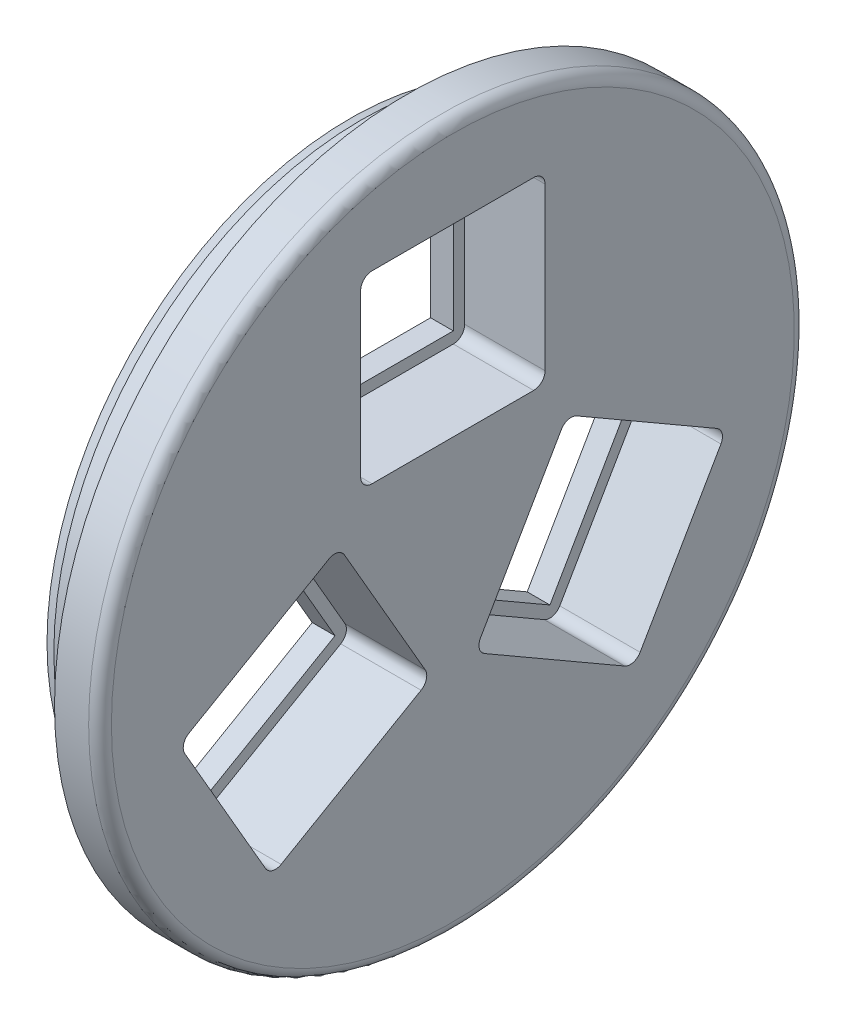
SolidWorks part; units mm, degrees
ref_plane "Front" through (0, 0, 0) normal (0, 0, 1) x (1, 0, 0)
ref_plane "Top" through (0, 0, 0) normal (0, 1, 0) x (1, 0, 0)
ref_plane "Right" through (0, 0, 0) normal (1, 0, 0) x (0, 0, -1)
sketch "Çizim1" plane through (0, 0, 0) normal (0, 0, 1) x (1, 0, 0)
  line L0 (0, 0) -> (45.3, 0) construction
  line L1 (48.1633, 0) -> (48.1633, 55.2041) construction
  line L2 (0, 0) -> (0, 55.2041) construction
  line L3 (0, 31) -> (5, 31)
  line L4 (0, 31) -> (0, 133)
  line L5 (5, 135) -> (25.3, 135)
  line L6 (25.3, 31) -> (25.3, 16)
  line L7 (25.3, 16) -> (35.3, 16)
  line L8 (45.3, 0) -> (45.3, 148.5)
  line L10 (40.3, 155) -> (25.3, 155)
  line L11 (25.3, 155) -> (25.3, 135)
  line L12 (7.3, 31) -> (25.3, 31)
  line L13 (5, 32.75) -> (7.3, 32.75)
  line L14 (5, 32.75) -> (5, 31)
  line L16 (7.3, 32.75) -> (7.3, 31)
  line L17 (0, 133) -> (5, 135)
  line L18 (35.3, 16) -> (35.3, 0)
  line L19 (35.3, 0) -> (45.3, 0)
  line L20 (45.3, 148.5) -> (45.3, 150)
  arc A0 (40.3, 155) -> (45.3, 150) centre (40.3, 150) cw
  point P8 (0, 135)
  point P24 (45.3, 155)
  dimension "D15" = 5
  dimension "D1" = 31
  dimension "D2" = 25.3
  dimension "D3" = 135
  dimension "D4" = 20
  dimension "D5" = 32
  dimension "D6" = 20
  dimension "D7" = 155
  dimension "D8" = 5
  dimension "D9" = 2.3
  dimension "D10" = 32.75
  dimension "D11" = 5
  dimension "D12" = 2
  dimension "D13" = 10
  dimension "D14" = 6.5
revolve "Döndür1" add sketch "Çizim1" angle 360 about L0
sketch "Sketch2" plane through (0, 0, 0) normal (-1, 0, 0) x (0, 0, 1)
  line L0 (0, 0) -> (0, 75)
  line L1 (-35.5, 110.5) -> (-35.5, 39.5)
  line L2 (-35.5, 115.5) -> (35.5, 115.5)
  line L3 (-40.5, 110.5) -> (-40.5, 39.5)
  line L4 (-35.5, 34.5) -> (35.5, 34.5)
  line L5 (40.5, 110.5) -> (40.5, 39.5)
  line L6 (-40.5, 115.5) -> (40.5, 34.5) construction
  line L7 (-40.5, 34.5) -> (40.5, 115.5) construction
  line L8 (-35.5, 39.5) -> (35.5, 39.5)
  line L9 (35.5, 110.5) -> (35.5, 39.5)
  line L10 (-35.5, 110.5) -> (35.5, 110.5)
  line L11 (115.9458, -20.176) -> (54.458, 15.324)
  line L12 (117.7759, -27.0061) -> (82.2759, -88.4939)
  line L13 (75.4458, -90.324) -> (13.958, -54.824)
  line L14 (47.6279, 13.4939) -> (12.1279, -47.9939)
  line L15 (-75.4458, -90.324) -> (-13.958, -54.824)
  line L16 (-82.2759, -88.4939) -> (-117.7759, -27.0061)
  line L17 (-115.9458, -20.176) -> (-54.458, 15.324)
  line L18 (-12.1279, -47.9939) -> (-47.6279, 13.4939)
  arc A0 (35.5, 115.5) -> (40.5, 110.5) centre (35.5, 110.5) cw
  arc A1 (35.5, 34.5) -> (40.5, 39.5) centre (35.5, 39.5) ccw
  arc A2 (-35.5, 34.5) -> (-40.5, 39.5) centre (-35.5, 39.5) cw
  arc A3 (-40.5, 110.5) -> (-35.5, 115.5) centre (-35.5, 110.5) cw
  arc A4 (-35.5, 39.5) -> (-35.5, 39.5) centre (-35.5, 39.5) cw
  arc A5 (35.5, 39.5) -> (35.5, 39.5) centre (35.5, 39.5) ccw
  arc A6 (35.5, 110.5) -> (35.5, 110.5) centre (35.5, 110.5) cw
  arc A7 (-35.5, 110.5) -> (-35.5, 110.5) centre (-35.5, 110.5) cw
  arc A8 (115.9458, -20.176) -> (117.7759, -27.0061) centre (113.4458, -24.5061) cw
  arc A9 (47.6279, 13.4939) -> (54.458, 15.324) centre (51.958, 10.9939) cw
  arc A10 (82.2759, -88.4939) -> (75.4458, -90.324) centre (77.9458, -85.9939) cw
  arc A11 (12.1279, -47.9939) -> (13.958, -54.824) centre (16.458, -50.4939) ccw
  arc A12 (-75.4458, -90.324) -> (-82.2759, -88.4939) centre (-77.9458, -85.9939) cw
  arc A13 (-12.1279, -47.9939) -> (-13.958, -54.824) centre (-16.458, -50.4939) cw
  arc A14 (-117.7759, -27.0061) -> (-115.9458, -20.176) centre (-113.4458, -24.5061) cw
  arc A15 (-47.6279, 13.4939) -> (-54.458, 15.324) centre (-51.958, 10.9939) ccw
  point P58 (0, 0)
  dimension "D3" = 5
  dimension "D1" = 81
  dimension "D2" = 81
  dimension "D4" = 5
extrude "Cut-Extrude2" cut sketch "Sketch2" against normal through all from offset 10 contours A3 L3 A2 L4 L8 L1 L10 L9 A1 L5 A0 L2 | L10 L1 L8 L9 | L14 A11 L13 A10 L12 A8 L11 A9 | L18 A15 L17 A14 L16 A12 L15 A13 region at (0, 40.5041, -17.75) region at (0, 35.6455, -17.75) region at (0, -37.5, 64.9519) region at (0, -37.5, -64.9519) offset against normal yes
sketch "Sketch4" plane through (0, 0, 0) normal (-1, 0, 0) x (0, 0, 1)
  line L0 (0, 0) -> (0, 75)
  line L1 (113.4458, -24.5061) -> (51.958, 10.9939)
  line L2 (-35.5, 110.5) -> (35.5, 110.5)
  line L3 (-35.5, 110.5) -> (-35.5, 39.5)
  line L4 (-35.5, 39.5) -> (35.5, 39.5)
  line L5 (35.5, 110.5) -> (35.5, 39.5)
  line L6 (-35.5, 110.5) -> (35.5, 39.5) construction
  line L7 (-35.5, 39.5) -> (35.5, 110.5) construction
  line L8 (113.4458, -24.5061) -> (77.9458, -85.9939)
  line L9 (77.9458, -85.9939) -> (16.458, -50.4939)
  line L10 (51.958, 10.9939) -> (16.458, -50.4939)
  line L11 (-77.9458, -85.9939) -> (-16.458, -50.4939)
  line L12 (-77.9458, -85.9939) -> (-113.4458, -24.5061)
  line L13 (-113.4458, -24.5061) -> (-51.958, 10.9939)
  line L14 (-16.458, -50.4939) -> (-51.958, 10.9939)
  point P17 (0, 0)
  dimension "D1" = 71
  dimension "D2" = 71
extrude "Cut-Extrude3" cut sketch "Sketch4" against normal through all contours L5 L2 L3 L4 | L1 L10 L9 L8 | L11 L14 L13 L12 region at (0, -37.5, 64.9519) region at (0, 109.4959, 0) region at (0, -37.5, -64.9519)
